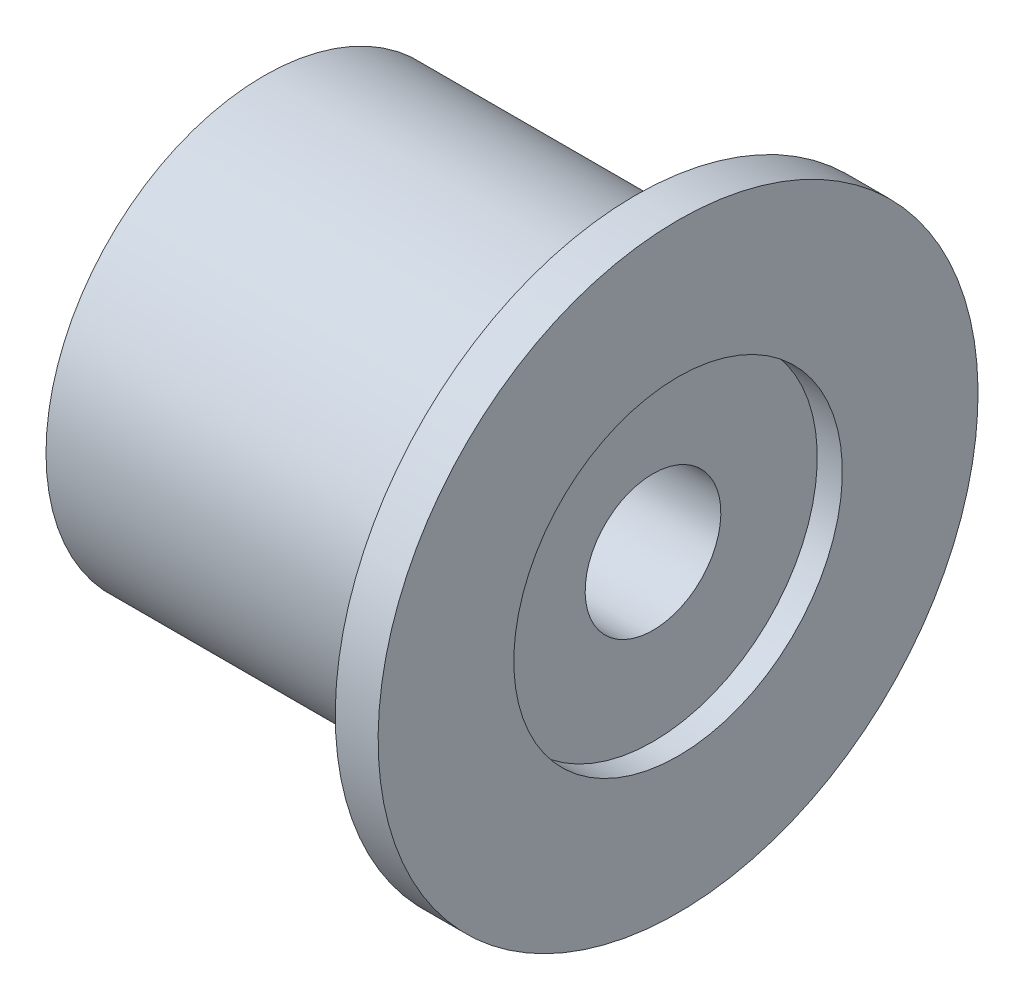
SolidWorks part; units mm, degrees
material "ABS"
ref_plane "Front" through (0, 0, 0) normal (0, 0, 1) x (1, 0, 0)
ref_plane "Top" through (0, 0, 0) normal (0, 1, 0) x (1, 0, 0)
ref_plane "Right" through (0, 0, 0) normal (1, 0, 0) x (0, 0, -1)
ref_axis "side-side" through (80.9, 0, 0) along (-1, 0, 0)
ref_axis "up-down" through (0, 50, 0) along (0, -1, 0)
ref_axis "front-back" through (0, 0, -80.9) along (0, 0, 1)
sketch "Sketch1" plane through (0, 0, 0) normal (0, 0, 1) x (1, 0, 0)
  line L0 (-15.24, 6.731) -> (-10.922, 2.413)
  line L3 (-1.4, 2.413) -> (-1.4, 5.842)
  line L4 (-1.4, 5.842) -> (-0.508, 5.842)
  line L8 (-2.032, 10.668) -> (-0.508, 10.668)
  line L9 (-2.032, 7.747) -> (-2.032, 10.668)
  line L10 (-15.24, 7.747) -> (-2.032, 7.747)
  line L11 (-0.508, 10.668) -> (-0.508, 5.842)
  line L12 (-1.4, 2.413) -> (-10.922, 2.413)
  line L13 (0, 0) -> (-22.0949, 0) construction
  line L15 (-15.24, 7.747) -> (-15.24, 6.731)
  line L16 (0, -50) -> (0, 50) construction
  point P4 (-8.636, 7.747)
  dimension "D1" = 4.826
  dimension "D2" = 15.494
  dimension "D3" = 21.336
  dimension "D4" = 15.24
  dimension "D5" = 2.032
  dimension "D6" = 1.016
  dimension "D7" = 45
  dimension "D8" = 1.4
  dimension "D9" = 11.684
  dimension "D10" = 0.508
revolve "Revolve1" add sketch "Sketch1" angle 360 about L13
